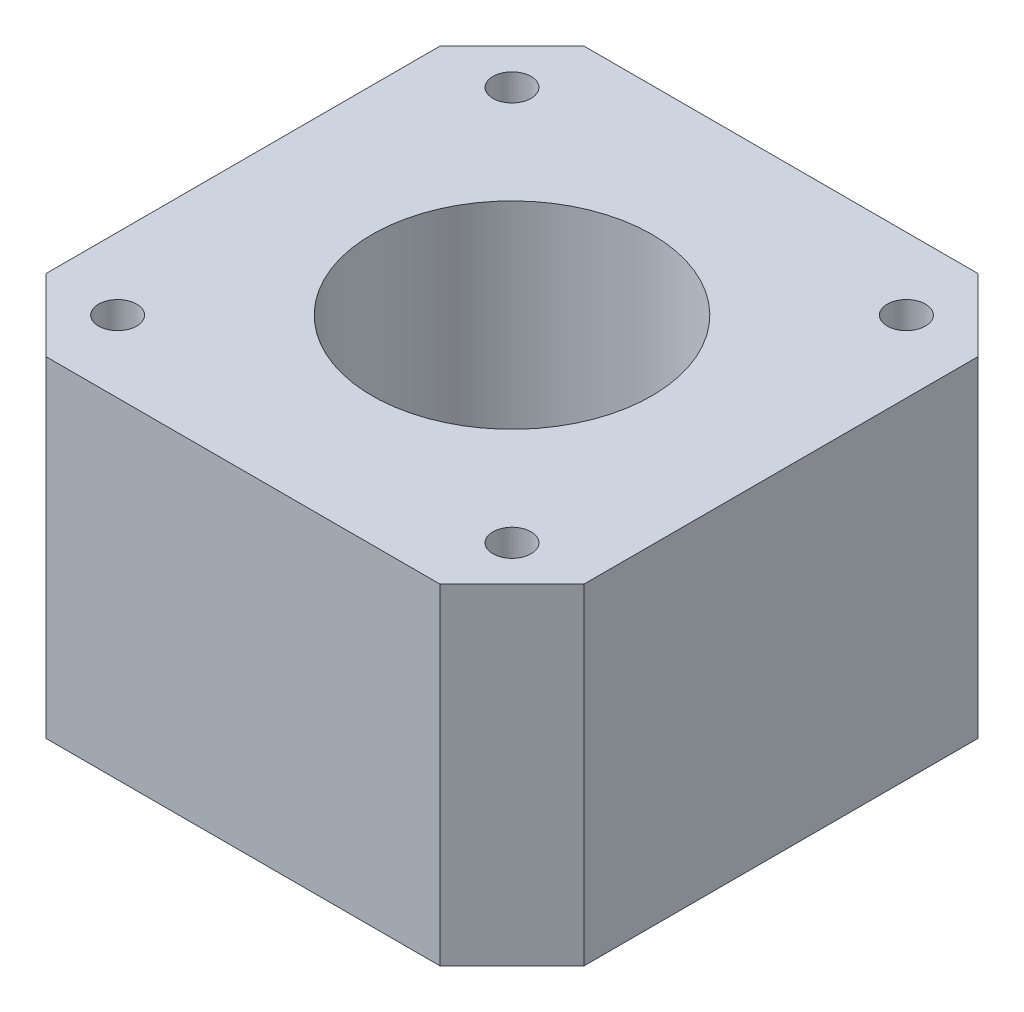
SolidWorks part; units mm, degrees
ref_plane "Front Plane" through (0, 0, 0) normal (0, 0, 1) x (1, 0, 0)
ref_plane "Top Plane" through (0, 0, 0) normal (0, 1, 0) x (1, 0, 0)
ref_plane "Right Plane" through (0, 0, 0) normal (1, 0, 0) x (0, 0, -1)
sketch "Sketch1" plane through (0, 0, 0) normal (0, 1, 0) x (1, 0, 0)
  line L0 (-21.15, 15.4931) -> (-15.4931, 21.15)
  line L1 (-21.15, 21.15) -> (21.15, 21.15)
  line L2 (-21.15, 21.15) -> (-21.15, -21.15)
  line L3 (-21.15, -21.15) -> (21.15, -21.15)
  line L4 (21.15, 21.15) -> (21.15, -21.15)
  line L5 (-21.15, 21.15) -> (21.15, -21.15) construction
  line L6 (-21.15, -21.15) -> (21.15, 21.15) construction
  line L7 (15.4931, 21.15) -> (21.15, 15.4931)
  line L8 (-21.15, -15.4931) -> (-15.4931, -21.15)
  line L9 (15.4931, -21.15) -> (21.15, -15.4931)
  line L11 (-15.505, 15.505) -> (15.505, 15.505) construction
  line L12 (-15.505, 15.505) -> (-15.505, -15.505) construction
  line L13 (-15.505, -15.505) -> (15.505, -15.505) construction
  line L14 (15.505, 15.505) -> (15.505, -15.505) construction
  line L15 (-15.505, 15.505) -> (15.505, -15.505) construction
  line L16 (-15.505, -15.505) -> (15.505, 15.505) construction
  circle A0 centre (-15.505, 15.505) radius 1.5
  circle A1 centre (15.505, 15.505) radius 1.5
  circle A2 centre (15.505, -15.505) radius 1.5
  circle A3 centre (-15.505, -15.505) radius 1.5
  circle A4 centre (0, 0) radius 11
  circle A5 centre (0, 0) radius 2.5
  point P0 (0, 0)
  point P14 (0, 0)
  point P23 (-18.3216, 18.3216)
  point P24 (18.3216, 18.3216)
  point P25 (-18.3216, -18.3216)
  point P26 (18.3216, -18.3216)
  dimension "D3" = 3
  dimension "D5" = 22
  dimension "D6" = 5
  dimension "D1" = 42.3
  dimension "D2" = 31.01
  dimension "D4" = 8
extrude "Boss-Extrude1" add sketch "Sketch1" along normal blind 26 contours L3 L9 L4 L7 L1 L0 L2 L8 A4 A3 A2 A1 A0 region at (-17.8986, 0, -17.8986)
extrude "Boss-Extrude2" add sketch "Sketch1<3>" along direction (0, 1, 0) on the side of the normal offset from surface (22.5 mm away) 3.5 contours A2 | A3 | A1 | A0 region at (15.505, 0, 15.505) up to face at (0, 26, 11)
sketch "Sketch1<3>" plane through (0, 0, 0) normal (0, 1, 0) x (1, 0, 0) same geometry as "Sketch1"
